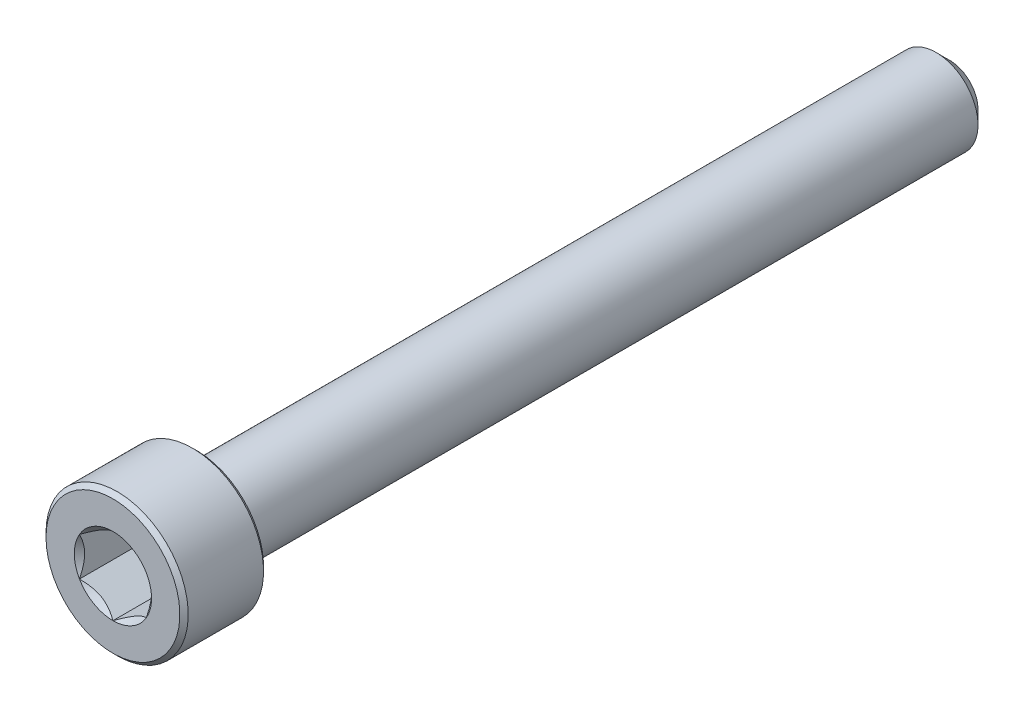
SolidWorks part; units mm, degrees
ref_plane "Front Plane" through (0, 0, 0) normal (0, 0, 1) x (1, 0, 0)
ref_plane "Top Plane" through (0, 0, 0) normal (0, 1, 0) x (1, 0, 0)
ref_plane "Right Plane" through (0, 0, 0) normal (1, 0, 0) x (0, 0, -1)
sketch "Sketch1" plane through (0, 0, 0) normal (1, 0, 0) x (0, 0, -1)
  line L0 (-25, 0) -> (25, 0) construction
  line L1 (25, 0) -> (25, 1.7) construction
  line L2 (25, 1.7) -> (24.2, 2.5) construction
  line L3 (24.2, 2.5) -> (24.4, 2.5) construction
  line L4 (24.4, 2.5) -> (-20, 2.5) construction
  line L5 (-20, 2.5) -> (-20, 4.25) construction
  line L6 (-20, 4.25) -> (-25, 4.25) construction
  line L7 (-25, 4.25) -> (-25, 0) construction
  line L8 (25, 1.7) -> (25, 2.5) construction
  line L9 (24.95, 2.5866) -> (25.35, 1.8938) construction
  line L10 (25.35, 1.8938) -> (25.75, 2.5866) construction
  line L11 (25.75, 2.5866) -> (24.95, 2.5866) construction
  line L12 (25.35, 2.5866) -> (25.35, 2.5) construction
  line L13 (25.35, 1.8938) -> (25.35, 1.9804) construction
  line L14 (25.3, 1.9804) -> (25.4, 1.9804) construction
  line L15 (25, 2.5) -> (25.7, 2.5) construction
  line L16 (24.975, 2.5433) -> (25.725, 2.5433) construction
  line L17 (25, 0) -> (25, -2.5) construction
  line L18 (-20.25, 4.25) -> (-20, 4) construction
  line L19 (-24.75, 4.25) -> (-25, 4) construction
  line L20 (-20, 2.5) -> (-20, 0) construction
  line L21 (-20, 1.25) -> (-5, 1.25) construction
  line L22 (-5, 1.25) -> (10, 1.25) construction
  line L23 (10, 1.25) -> (25, 1.25) construction
  line L24 (-5, 1.25) -> (-5, 2.5) construction
  line L25 (-5, 2.5) -> (-5, 4.25) construction
  line L26 (10, 1.25) -> (10, 4.25) construction
  point P0 (-25, 2)
  point P3 (23, 2.5)
  point P4 (0, 0)
  point P18 (10, 2.5)
  point P22 (25.35, 1.9804)
  point P24 (24.4, 2.5)
  point P25 (25.35, 2.5)
  point P28 (25.35, 2.5433)
  point P29 (23, -2.5)
  point P30 (-5, 2.5)
  point P31 (-22.5, 4.25)
  point P37 (-20.875, 4.25)
  point P38 (-24.625, 4.25)
  point P45 (-5, 1.25)
  point P46 (10, 1.25)
  dimension "D1" = 45
  dimension "D2" = 0.1
  dimension "D3" = 0.8
  dimension "D7" = 0.25
  dimension "D8" = 0.25
  dimension "D9" = 0.25
  dimension "D10" = 0.125
  dimension "D11" = 0.625
  dimension "Drive Size" = 4
  dimension "Head Diameter" = 8.5
  dimension "Head Height" = 5
  dimension "Thread Pitch" = 0.8
  dimension "Thread Major Diameter" = 5
  dimension "Length" = 45
  dimension "D12" = 0.6
  dimension "D4" = 2
sketch "Sketch2" plane through (0, 0, 0) normal (1, 0, 0) x (0, 0, -1)
  line L0 (-25, 0) -> (-25, 4)
  line L1 (-24.75, 4.25) -> (-20.25, 4.25)
  line L2 (-20, 4) -> (-20, 2.5)
  line L3 (-20, 2.5) -> (24.2, 2.5)
  line L4 (24.2, 2.5) -> (25, 1.7)
  line L5 (25, 1.7) -> (25, 0)
  line L6 (-20.25, 4.25) -> (-20, 4) construction
  line L7 (25, 0) -> (-25, 0)
  line L8 (-24.75, 4.25) -> (-25, 4) construction
  line L9 (-20.25, 4.25) -> (-20, 4)
  line L10 (-24.75, 4.25) -> (-25, 4)
revolve "Revolve1" add sketch "Sketch2" angle 360 about L7
sketch "Sketch3" plane through (0, 0, 25) normal (0, 0, 1) x (1, 0, 0)
  line L1 (2, -1.1547) -> (2, 1.1547)
  line L2 (2, 1.1547) -> (0, 2.3094)
  line L3 (0, 2.3094) -> (-2, 1.1547)
  line L4 (-2, 1.1547) -> (-2, -1.1547)
  line L5 (-2, -1.1547) -> (0, -2.3094)
  line L6 (0, -2.3094) -> (2, -1.1547)
  circle A0 centre (0, 0) radius 2 construction
extrude "Cut-Extrude1" cut sketch "Sketch3" against normal offset from surface (4 mm away) 1 up to face at (-4, 0, 20)
sketch "Sketch4" plane through (0, 0, 25) normal (0, 0, 1) x (1, 0, 0)
  circle A0 centre (0, 0) radius 2.3094
extrude "Cut-Extrude2" cut sketch "Sketch4" against normal up to vertex (2.5 mm away) draft 45 up to point (0, 4.25, 22.5)
ref_plane "Plane1" [suppressed] through (0, 0, -24.4) normal (0, 0, 1) x (1, 0, 0)
split "Split1" [suppressed] bodies to split 106
sketch "Sketch6" [suppressed] plane through (0, 0, -25) normal (0, 0, -1) x (-1, 0, 0)
  circle A0 centre (0, 0) radius 2.5
curve "Helix/Spiral1" [suppressed] pitch 0.8 height 45.92 turns 57.4
sketch "Sketch7" [suppressed] plane through (0, 0, 0) normal (1, 0, 0) x (0, 0, -1)
  line L0 (24.975, 2.5433) -> (25.725, 2.5433)
  line L1 (25.725, 2.5433) -> (25.4, 1.9804)
  line L2 (25.4, 1.9804) -> (25.3, 1.9804)
  line L3 (25.3, 1.9804) -> (24.975, 2.5433)
sweep "Cut-Sweep1" [suppressed] cut profiles "Sketch7" path "Helix/Spiral1"
sketch "Sketch8" [suppressed] plane through (0, 0, 20) normal (0, 0, -1) x (-1, 0, 0)
  circle A0 centre (0, 0) radius 2.5
extrude "Boss-Extrude1" [suppressed] add sketch "Sketch8" along normal through all draft 45
equation "\"D2@Sketch1\" = \"Thread Pitch@Sketch1\" / 8"
equation "\"D3@Sketch1\"= \"Thread Pitch@Sketch1\""
equation "\"D4@Helix/Spiral1\" = \"Thread Pitch@Sketch1\""
equation "\"D7@Sketch1\" = \"Head Height@Sketch1\" * .05"
equation "\"D8@Sketch1\"=\"D7@Sketch1\""
equation "\"D9@Sketch1\"=\"D7@Sketch1\""
equation "\"D10@Sketch1\"=\"D7@Sketch1\"/2"
equation "\"D11@Sketch1\"=\"D10@Sketch1\"*5"
equation "\"D4@Sketch1\"=\"Thread Pitch@Sketch1\"*2.5"
equation "\"D12@Sketch1\"=\"Thread Pitch@Sketch1\"*.75"
